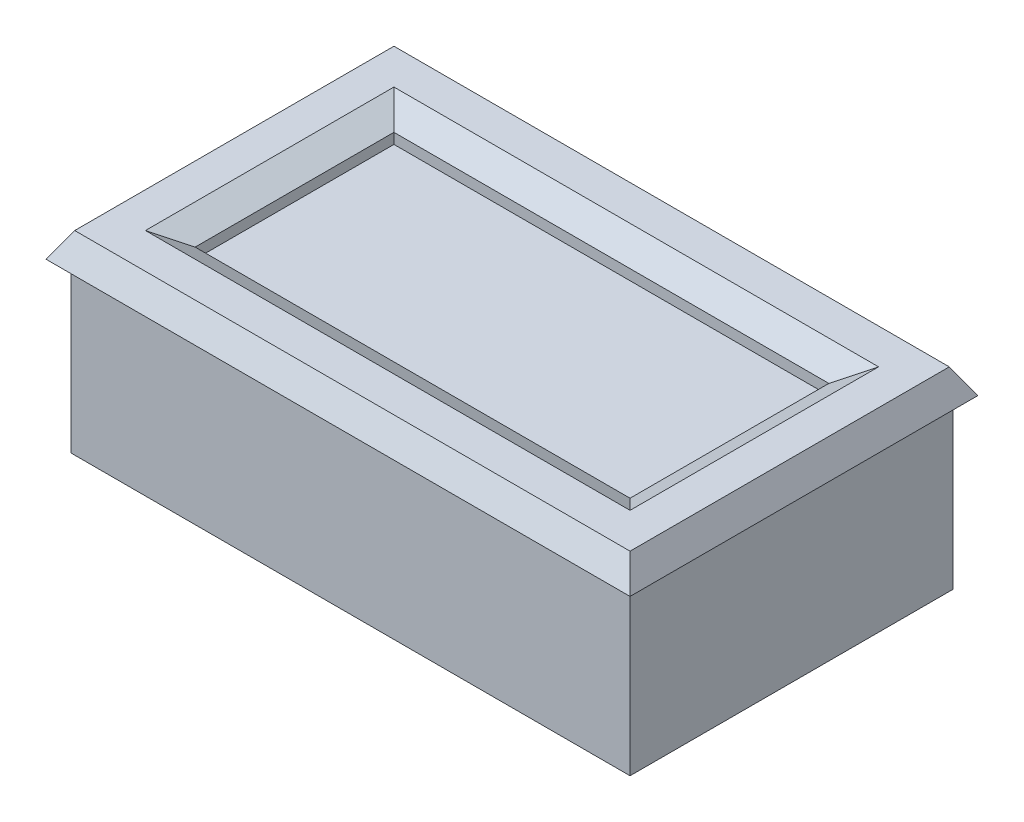
SolidWorks part; units mm, degrees
ref_plane "Front Plane" through (0, 0, 0) normal (0, 0, 1) x (1, 0, 0)
ref_plane "Top Plane" through (0, 0, 0) normal (0, 1, 0) x (1, 0, 0)
ref_plane "Right Plane" through (0, 0, 0) normal (1, 0, 0) x (0, 0, -1)
sketch "Sketch1" plane through (0, 0, 0) normal (0, 1, 0) x (1, 0, 0)
  line L1 (-22.5, -13) -> (22.5, -13)
  line L2 (-22.5, -13) -> (-22.5, 13)
  line L3 (-22.5, 13) -> (22.5, 13)
  line L4 (22.5, -13) -> (22.5, 13)
  line L5 (-22.5, -13) -> (22.5, 13) construction
  line L6 (-22.5, 13) -> (22.5, -13) construction
  point P0 (0, 0)
  dimension "D1" = 45
  dimension "D2" = 26
extrude "Boss-Extrude1" add sketch "Sketch1" along normal blind 13.5
sketch "Sketch2" plane through (0, 13.5, 0) normal (0, 1, 0) x (1, 0, 0)
  line L4 (17.5, -8) -> (17.5, 8)
  line L8 (23.5, -14) -> (23.5, 14)
  line L9 (23.5, 14) -> (-23.5, 14)
  line L10 (-23.5, 14) -> (-23.5, -14)
  line L11 (-23.5, -14) -> (23.5, -14)
  line L12 (23.5, -14) -> (23.5, 14)
  line L13 (23.5, 14) -> (-23.5, 14)
  line L14 (-23.5, 14) -> (-23.5, -14)
  line L15 (-23.5, -14) -> (23.5, -14)
  line L17 (17.5, 8) -> (-17.5, 8)
  line L18 (-17.5, 8) -> (-17.5, -8)
  line L19 (-17.5, -8) -> (17.5, -8)
  point P0 (0, 0)
  dimension "D2" = 6
  dimension "D1" = 1
extrude "Boss-Extrude2" add sketch "Sketch2" along normal blind 2
chamfer "Chamfer1" distance 2 angle 30 8 edges at (0, 15.5, -8) (-17.5, 15.5, 0) (0, 15.5, 8) (17.5, 15.5, 0) (-23.5, 15.5, 0) (0, 15.5, -14) (23.5, 15.5, 0) (0, 15.5, 14)
sketch "Sketch3" plane through (0, 0, 0) normal (0, -1, 0) x (1, 0, 0)
  line L0 (-22, -4) -> (-19.5, -4)
  line L2 (-22, -7) -> (-19.5, -7)
  line L3 (-22, -7) -> (-22, -4)
  line L4 (22.5, -13) -> (-22.5, -13) construction
  line L5 (-22.5, -13) -> (-22.5, 13) construction
  arc A0 (-19.5, -4) -> (-19.5, -7) centre (-19.5, -5.5) cw
  dimension "D1" = 4
  dimension "D2" = 3
  dimension "D3" = 6
  dimension "D4" = 0.5
extrude "Cut-Extrude1" cut sketch "Sketch3" against normal up to surface (13.5 mm away) up to face at (0, 13.5, 0)
